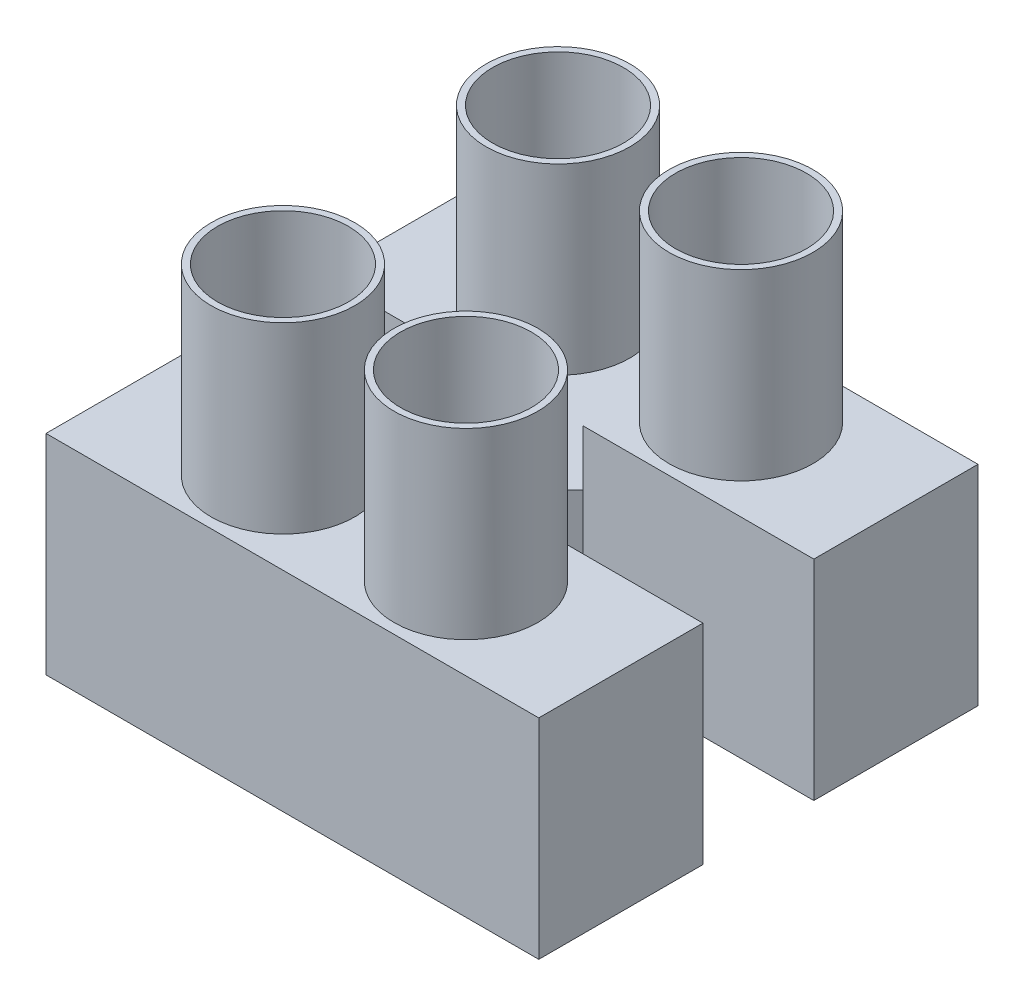
SolidWorks part; units mm, degrees
ref_plane "Front Plane" through (0, 0, 0) normal (0, 0, 1) x (1, 0, 0)
ref_plane "Top Plane" through (0, 0, 0) normal (0, 1, 0) x (1, 0, 0)
ref_plane "Right Plane" through (0, 0, 0) normal (1, 0, 0) x (0, 0, -1)
sketch "Sketch1" plane through (0, 0, 0) normal (0, 1, 0) x (1, 0, 0)
  line L0 (-0.2547, 4.4323) -> (1.8666, 6.5536)
  line L1 (-9.6797, 4.4323) -> (9.1703, 4.4323)
  line L2 (-9.6797, 4.4323) -> (-9.6797, -1.8477)
  line L3 (-9.6797, -1.8477) -> (9.1703, -1.8477)
  line L4 (9.1703, 4.4323) -> (9.1703, -1.8477)
  line L5 (1.8666, 6.5536) -> (2.4666, 6.5536)
  line L6 (2.4666, 6.5536) -> (0.3453, 4.4323)
  line L8 (-2.9761, 6.5536) -> (-0.8547, 4.4323)
  line L9 (-2.3761, 6.5536) -> (-2.9761, 6.5536)
  line L10 (-0.2547, 4.4323) -> (-2.3761, 6.5536)
  line L11 (-0.2547, 8.6749) -> (-2.3761, 6.5536)
  line L12 (-2.9761, 6.5536) -> (-0.8547, 8.6749)
  line L13 (2.4666, 6.5536) -> (0.3453, 8.6749)
  line L14 (9.1703, 8.6749) -> (9.1703, 14.9549)
  line L15 (-9.6797, 14.9549) -> (9.1703, 14.9549)
  line L16 (-9.6797, 8.6749) -> (-9.6797, 14.9549)
  line L17 (-9.6797, 8.6749) -> (9.1703, 8.6749)
  line L18 (-0.2547, 8.6749) -> (1.8666, 6.5536)
  dimension "D1" = 18.85
  dimension "D2" = 6.28
  dimension "D3" = 3
  dimension "D4" = 3
  dimension "D5" = 135
  dimension "D6" = 0.6
extrude "Boss-Extrude1" add sketch "Sketch1" along normal blind 8 contours L1 L4 L3 L2
extrude "Boss-Extrude2" add sketch "Sketch1<3>" along normal blind 8 separate body contours L16 L17 L14 L15 region at (-0.2547, 0, -11.8149)
sketch "Sketch1<3>" plane through (0, 0, 0) normal (0, 1, 0) x (1, 0, 0) same geometry as "Sketch1"
extrude "Boss-Extrude3" add sketch "Sketch1<5>" along normal blind 8 contours L17 L12 L9 L11 | L1 L10 L9 L8 | L17 L18 L5 L13 | L6 L5 L0 L1 region at (1.1059, 0, -5.493) region at (-1.6154, 0, -5.493) region at (1.1059, 0, -7.6143) region at (-1.6154, 0, -7.6143)
sketch "Sketch1<5>" plane through (0, 0, 0) normal (0, 1, 0) x (1, 0, 0) same geometry as "Sketch1"
sketch "Sketch2" plane through (0, 0, 0) normal (0, 1, 0) x (1, 0, 0)
  line L0 (9.1703, 11.8149) -> (-9.6797, 11.8149) construction
  line L1 (9.1703, 8.6749) -> (9.1703, 14.9549) construction
  line L2 (-9.6797, 8.6749) -> (-9.6797, 14.9549) construction
  line L3 (-0.2547, 14.9549) -> (-0.2547, -1.8477) construction
  line L4 (-9.6797, 14.9549) -> (9.1703, 14.9549) construction
  line L5 (-9.6797, -1.8477) -> (9.1703, -1.8477) construction
  circle A0 centre (3.2453, 11.8149) radius 2.75
  circle A1 centre (3.2453, 11.8149) radius 2.505
  dimension "D1" = 5.5
  dimension "D2" = 3.5
extrude "Boss-Extrude5" add sketch "Sketch2" along normal blind 15
ref_plane "Plane1" through (-0.2547, 0, 0) normal (1, 0, 0) x (0, 0, -1)
mirror "Mirror1" about plane through (-0.2547, 0, 0) normal (1, 0, 0) of "Boss-Extrude5"
ref_plane "Plane2" through (0, 0, -6.5536) normal (0, 0, -1) x (-1, 0, 0)
mirror "Mirror2" about plane through (0, 0, -6.5536) normal (0, 0, -1) of "Mirror1", "Boss-Extrude5"
